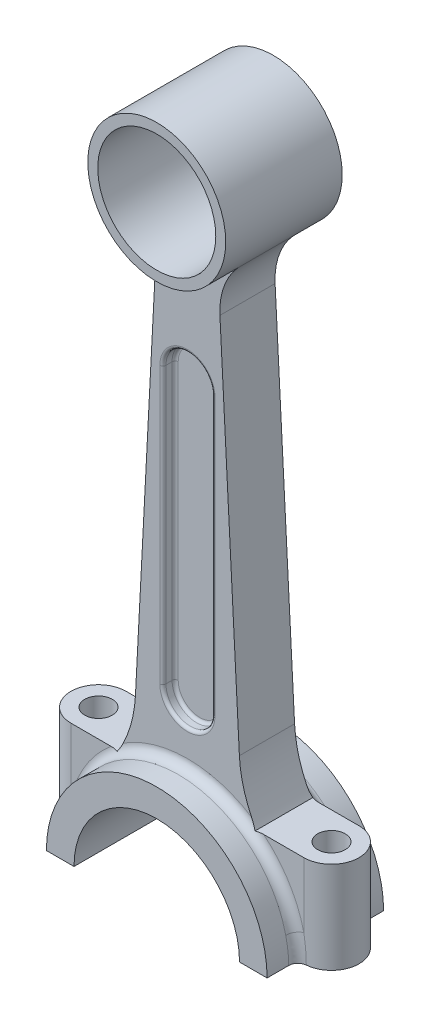
SolidWorks part; units mm, degrees
ref_plane "Front Plane" through (0, 0, 0) normal (0, 0, 1) x (1, 0, 0)
ref_plane "Top Plane" through (0, 0, 0) normal (0, 1, 0) x (1, 0, 0)
ref_plane "Right Plane" through (0, 0, 0) normal (1, 0, 0) x (0, 0, -1)
sketch "Sketch1" plane through (0, 0, 0) normal (0, 0, 1) x (1, 0, 0)
  line L0 (0, 0) -> (0, -201.2) construction
  line L1 (-10, -20.1556) -> (-17.8497, -169.9368)
  line L2 (10, -20.1556) -> (17.8497, -169.9368)
  line L3 (-36, -201.2) -> (-27, -201.2)
  line L4 (27, -201.2) -> (36, -201.2)
  circle A0 centre (0, 0) radius 19.25
  circle A1 centre (0, 0) radius 22.5
  arc A2 (27, -201.2) -> (-27, -201.2) centre (0, -201.2) ccw
  arc A3 (36, -201.2) -> (-36, -201.2) centre (0, -201.2) ccw
  dimension "D1" = 38.5
  dimension "D2" = 54
  dimension "D3" = 72
  dimension "D7" = 45
  dimension "D4" = 201.2
  dimension "D5" = 20
  dimension "D6" = 6
extrude "Boss-Extrude1" add sketch "Sketch1" along normal mid plane 38 contours A0 A1 | A3 A2 | L3 A2 L4 A3 region at (-11.5231, 18.5805, 0) region at (0, -166.005, 0)
extrude "Boss-Extrude2" add sketch "Sketch1<3>" along normal mid plane 18 contours A1 L0 A3 L2 | L0 A1 L1 A3 region at (7.1843, -100.8455, 0) region at (-7.1843, -100.8455, 0)
sketch "Sketch1<3>" plane through (0, 0, 0) normal (0, 0, 1) x (1, 0, 0) same geometry as "Sketch1"
sketch "Sketch2" plane through (0, 0, 9) normal (0, 0, 1) x (1, 0, 0)
  line L0 (0, 0) -> (0, -201.2) construction
  line L1 (0, -55.6) -> (0, -145.6) construction
  line L2 (8, -55.6) -> (8, -145.6)
  line L3 (-8, -55.6) -> (-8, -145.6)
  arc A0 (8, -55.6) -> (-8, -55.6) centre (0, -55.6) ccw
  arc A1 (-8, -145.6) -> (8, -145.6) centre (0, -145.6) ccw
  point P6 (0, -100.6)
  dimension "D1" = 8
  dimension "D2" = 90
extrude "Cut-Extrude1" cut sketch "Sketch2" against normal blind 4
mirror "Mirror1" about plane through (0, 0, 0) normal (0, 0, 1) of "Cut-Extrude1"
fillet "Fillet1" radius 1 16 edges at (8, -100.6, -9) (0, -153.6, -9) (-8, -100.6, -9) (8, -100.6, 9) (0, -153.6, 9) (-8, -100.6, 9) (8, -100.6, 5) (0, -153.6, 5) (-8, -100.6, 5) (0, -47.6, 5) (-8, -100.6, -5) (0, -153.6, -5) (8, -100.6, -5) (0, -47.6, -5) (0, -47.6, -9) (0, -47.6, 9)
fillet "Fillet2" radius 40 2 edges at (17.8497, -169.9368, 0) (-17.8497, -169.9368, 0)
fillet "Fillet3" radius 22.5 2 edges at (10, -20.1556, 0) (-10, -20.1556, 0)
ref_plane "Plane1" through (0, -171.2, 0) normal (0, -1, 0) x (-1, 0, 0)
sketch "Sketch4" plane through (0, -171.2, 0) normal (0, -1, 0) x (-1, 0, 0)
  line L0 (38, 0) -> (-38, 0) construction
  line L1 (38, -9) -> (-38, -9)
  line L2 (38, 9) -> (-38, 9)
  arc A0 (38, -9) -> (38, 9) centre (38, 0) ccw
  arc A1 (-38, 9) -> (-38, -9) centre (-38, 0) ccw
  point P2 (0, 0)
  dimension "D2" = 9
  dimension "D1" = 76
extrude "Boss-Extrude3" add sketch "Sketch4" along normal up to surface (30 mm away) up to face at (-31.5, -201.2, 0)
sketch "Sketch5" plane through (0, 0, 9) normal (0, 0, 1) x (1, 0, 0)
  line L1 (-27, -201.2) -> (27, -201.2)
  line L2 (-27, -201.2) -> (27, -201.2)
  arc A1 (27, -201.2) -> (-27, -201.2) centre (0, -201.2) ccw
  arc A2 (27, -201.2) -> (-27, -201.2) centre (0, -201.2) ccw
  dimension "D1" = 0
extrude "Cut-Extrude2" cut sketch "Sketch5" against normal through all both and the other way through all
sketch "Sketch7" plane through (0, -171.2, 0) normal (0, 1, 0) x (1, 0, 0)
  circle A2 centre (-38, 0) radius 4.5
  circle A3 centre (38, 0) radius 4.5
  dimension "D1" = 9
  dimension "D2" = 9
fillet "Fillet4" radius 3 2 edges at (0, -165.2, -9) (0, -165.2, 9)
extrude "Cut-Extrude4" cut sketch "Sketch7" against normal through all
